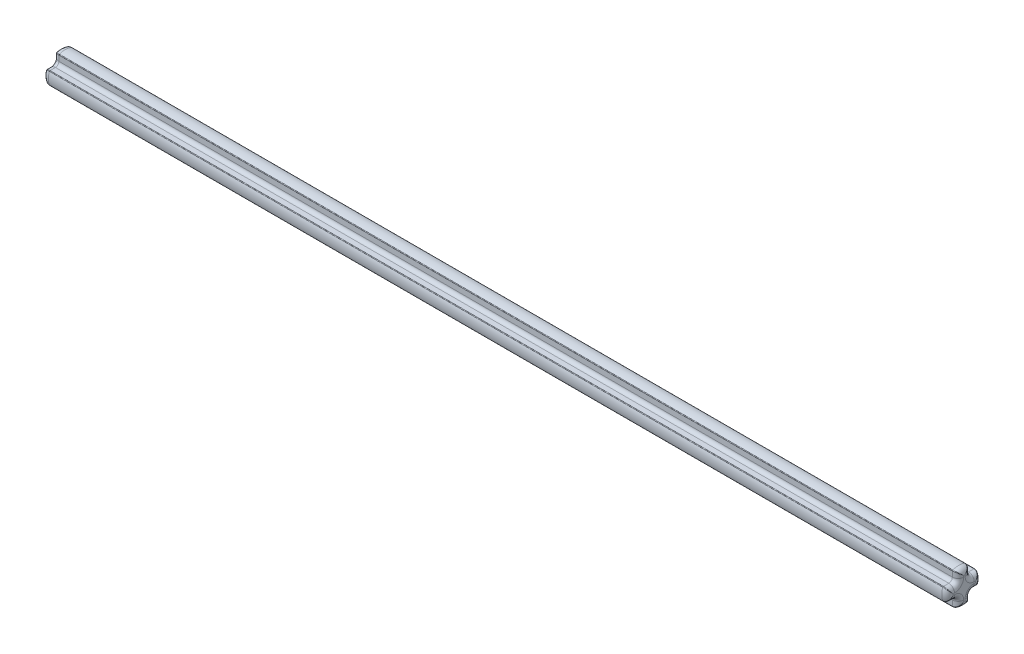
SolidWorks part; units mm, degrees
material "PET"
ref_plane "Alzado" through (0, 0, 0) normal (0, 0, 1) x (1, 0, 0)
ref_plane "Planta" through (0, 0, 0) normal (0, 1, 0) x (1, 0, 0)
ref_plane "Vista lateral" through (0, 0, 0) normal (1, 0, 0) x (0, 0, -1)
sketch "Croquis1" plane through (0, 0, 0) normal (1, 0, 0) x (0, 0, -1)
  line B0 (-1.4, 0.9) -> (-2.1564, 0.9)
  line B1 (0.9, -2.1564) -> (0.9, -1.4)
  line B2 (-0.9, -2.1564) -> (-0.9, -1.4)
  line B3 (2.1564, 0.9) -> (1.4, 0.9)
  line B4 (2.1564, -0.9) -> (1.4, -0.9)
  line B5 (-0.9, 1.4) -> (-0.9, 2.1564)
  line B6 (0.9, 1.4) -> (0.9, 2.1564)
  line B7 (-1.4, -0.9) -> (-2.1564, -0.9)
  arc B8 (-2.2501, 0.8348) -> (-2.2501, -0.8348) centre (0, 0) ccw
  arc B9 (-1.4, -0.9) -> (-0.9, -1.4) centre (-1.4, -1.4) cw
  arc B10 (0.9, -1.4) -> (1.4, -0.9) centre (1.4, -1.4) cw
  arc B11 (1.4, 0.9) -> (0.9, 1.4) centre (1.4, 1.4) cw
  arc B12 (-0.9, 1.4) -> (-1.4, 0.9) centre (-1.4, 1.4) cw
  arc B13 (0.8348, 2.2501) -> (-0.8348, 2.2501) centre (0, 0) ccw
  arc B14 (2.2501, -0.8348) -> (2.2501, 0.8348) centre (0, 0) ccw
  arc B15 (-0.8348, -2.2501) -> (0.8348, -2.2501) centre (0, 0) ccw
  arc B16 (-0.8348, 2.2501) -> (-0.9, 2.1564) centre (-0.8, 2.1564) ccw
  arc B17 (0.8348, 2.2501) -> (0.9, 2.1564) centre (0.8, 2.1564) cw
  arc B18 (2.2501, 0.8348) -> (2.1564, 0.9) centre (2.1564, 0.8) ccw
  arc B19 (2.2501, -0.8348) -> (2.1564, -0.9) centre (2.1564, -0.8) cw
  arc B20 (0.9, -2.1564) -> (0.8348, -2.2501) centre (0.8, -2.1564) cw
  arc B21 (-0.8348, -2.2501) -> (-0.9, -2.1564) centre (-0.8, -2.1564) cw
  arc B22 (-2.1564, -0.9) -> (-2.2501, -0.8348) centre (-2.1564, -0.8) cw
  arc B23 (-2.1564, 0.9) -> (-2.2501, 0.8348) centre (-2.1564, 0.8) ccw
sketch_block_instance "Axle Section Block Rounded 0.1 mm-1"
sketch_block "Axle Section Block Rounded 0.1 mm" parameters "D1"=4.8, "D3"=0.5, "D4"=0.1, "D2"=1.8
extrude "Saliente-Extruir1" add sketch "Croquis1" along normal blind 128
fillet "Redondeo1" radius 0.8 48 edges at (0, 1.7782, 0.9) (0, 1.0464, 1.0464) (0, 0.9, 1.7782) (0, 0.8821, 2.2135) (0, 0, 2.4) (0, -0.8821, 2.2135) (0, -0.9, 1.7782) (0, -1.0464, 1.0464) (0, -1.7782, 0.9) (0, -2.2135, 0.8821) (0, -2.4, 0) (0, -2.2135, -0.8821) (0, -1.7782, -0.9) (0, -1.0464, -1.0464) (0, -0.9, -1.7782) (0, -0.8821, -2.2135) (0, 0, -2.4) (0, 0.8821, -2.2135) (0, 0.9, -1.7782) (0, 1.0464, -1.0464) (0, 1.7782, -0.9) (0, 2.2135, -0.8821) (0, 2.4, 0) (0, 2.2135, 0.8821) (128, 2.4, 0) (128, 2.2135, -0.8821) (128, 1.7782, -0.9) (128, 1.0464, -1.0464) (128, 0.9, -1.7782) (128, 0.8821, -2.2135) (128, 0, -2.4) (128, -0.8821, -2.2135) (128, -0.9, -1.7782) (128, -1.0464, -1.0464) (128, -1.7782, -0.9) (128, -2.2135, -0.8821) (128, -2.4, 0) (128, -2.2135, 0.8821) (128, -1.7782, 0.9) (128, -1.0464, 1.0464) (128, -0.9, 1.7782) (128, -0.8821, 2.2135) (128, 0, 2.4) (128, 0.8821, 2.2135) (128, 0.9, 1.7782) (128, 1.0464, 1.0464) (128, 1.7782, 0.9) (128, 2.2135, 0.8821)
